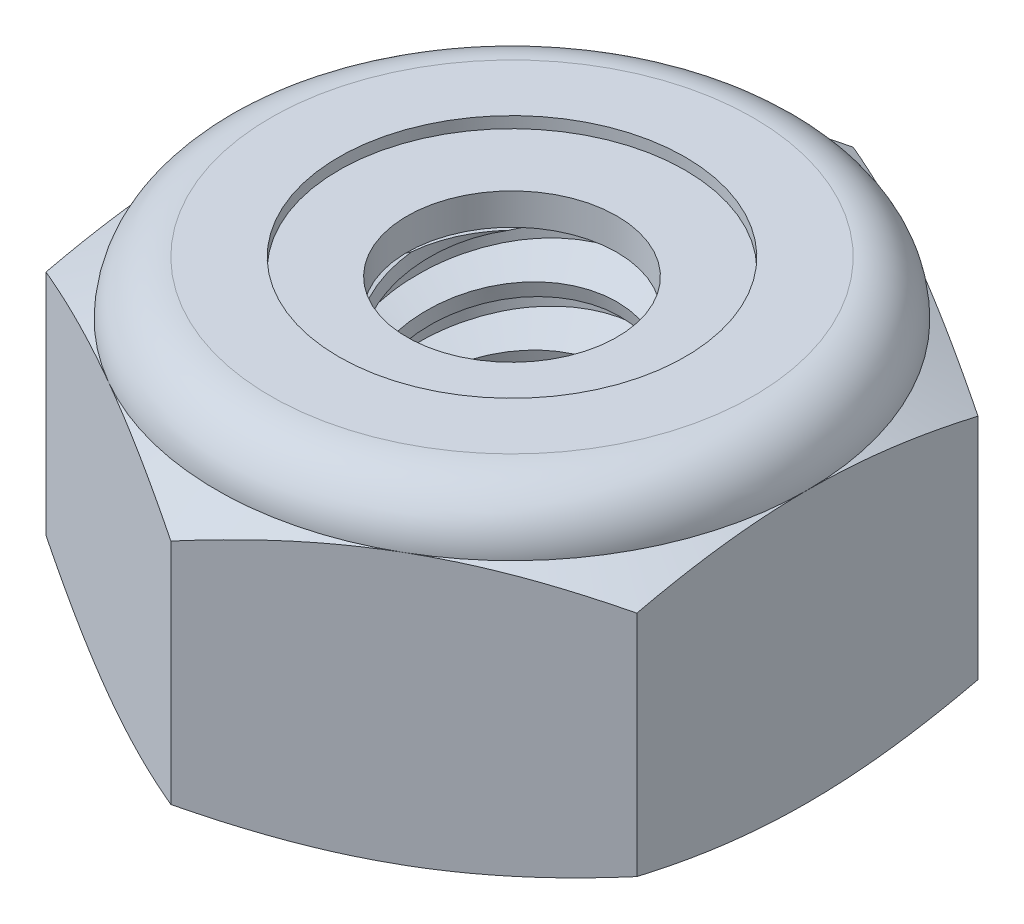
SolidWorks part; units mm, degrees
material "Alloy Steel"
ref_plane "Front" through (0, 0, 0) normal (0, 0, 1) x (1, 0, 0)
ref_plane "Top" through (0, 0, 0) normal (0, 1, 0) x (1, 0, 0)
ref_plane "Right" through (0, 0, 0) normal (1, 0, 0) x (0, 0, -1)
sketch "Sketch1" plane through (0, 0, 0) normal (0, 1, 0) x (1, 0, 0)
  line L1 (0, 4.5827) -> (-3.9688, 2.2914)
  line L2 (-3.9688, 2.2914) -> (-3.9688, -2.2914)
  line L3 (-3.9688, -2.2914) -> (0, -4.5827)
  line L4 (0, -4.5827) -> (3.9688, -2.2914)
  line L5 (3.9688, -2.2914) -> (3.9687, 2.2914)
  line L6 (3.9687, 2.2914) -> (0, 4.5827)
  circle A0 centre (0, 0) radius 3.9688 construction
  dimension "Hex Flats" = 7.9375
extrude "Extrude1" add sketch "Sketch1" along normal blind 4.3656
sketch "Sketch2" plane through (0, 0, 0) normal (1, 0, 0) x (0, 0, -1)
  line L0 (-1.7526, 0) -> (-1.7526, 4.3656) construction
  line L1 (0, 0) -> (1.7526, 0)
  line L2 (0, 0) -> (0, 4.3656)
  line L3 (0, 4.3656) -> (1.7526, 4.3656)
  line L4 (1.7526, 0) -> (1.7526, 4.3656)
  line L5 (-2.2914, 4.3656) -> (2.2914, 4.3656) construction
  line L7 (0, -1.7526) -> (0, 0) construction
  dimension "Thread Dia" = 3.5052
revolve "Revolve1" add sketch "Sketch2" angle 360 about L7
sketch "Sketch3" plane through (0, 0, 0) normal (1, 0, 0) x (0, 0, -1)
  line L0 (1.7526, 4.3656) -> (-1.7526, 4.3656) construction
  line L1 (-1.7526, 4.3656) -> (-1.7526, 3.5719) construction
  line L2 (-1.7526, 3.5719) -> (1.7526, 4.3656) construction
  line L3 (1.7526, 4.3656) -> (1.7745, 4.2689) construction
  line L4 (1.7745, 4.2689) -> (1.9279, 3.5915)
  line L5 (1.9279, 3.5915) -> (1.4541, 3.7385)
  line L6 (1.4541, 3.7385) -> (1.4103, 3.932)
  line L7 (1.4103, 3.932) -> (1.7745, 4.2689)
  line L8 (1.4322, 3.8353) -> (1.8512, 3.9302) construction
  line L9 (1.7526, 4.3656) -> (1.7526, 3.9078) construction
  line L10 (1.7526, 3.9078) -> (-1.7526, 3.1141) construction
  line L11 (-1.7526, 3.1141) -> (-1.7526, 3.5719) construction
  line L12 (-0.1935, 4.3656) -> (0.1935, 2.6563) construction
  line L13 (-1.7526, 0) -> (-1.7526, 4.3656) construction
  line L14 (0, 4.3656) -> (1.7526, 4.3656) construction
  line L15 (1.7526, 0) -> (1.7526, 4.3656) construction
  point P13 (0, 3.511)
  dimension "D1" = 0.0992
  dimension "D2" = 0.1984
  dimension "Thread Pitch" = 0.7937
  dimension "D4" = 60
  dimension "D5" = 0.7937
revolve "Cut-Revolve1" cut sketch "Sketch3" angle 360 about L12
pattern_linear "LPattern1" count 6 spacing 0.7937 along (0, -1, 0) count 2 spacing 0.7937 along (0, 1, 0) of "Cut-Revolve1"
sketch "Sketch4" plane through (0, 0, 0) normal (1, 0, 0) x (0, 0, -1)
  line L0 (0, 4.3656) -> (1.7526, 4.3656)
  line L1 (1.7526, 4.3656) -> (1.4103, 4.206)
  line L2 (1.4103, 4.206) -> (1.4103, 0.1596)
  line L3 (1.4103, 0.1596) -> (1.7526, 0)
  line L4 (1.7526, 0) -> (0, 0)
  line L5 (0, 0) -> (0, 4.3656)
  line L6 (1.7526, 0) -> (1.7526, 4.3656) construction
  line L7 (0, 4.3656) -> (1.7526, 4.3656) construction
  line L8 (0, 0) -> (1.7526, 0) construction
  line L9 (0, 0) -> (0, 4.3656) construction
  line L10 (0, 4.3656) -> (0, 4.7433) construction
  dimension "D1" = 25
revolve "Cut-Revolve2" cut sketch "Sketch4" angle 360 about L10
combine bodies "Combine1" operation type subtract main body 112 bodies to subtract 111
sketch "Sketch5" plane through (0, 0, 0) normal (1, 0, 0) x (0, 0, -1)
  line L0 (0, 0) -> (3.9688, 0)
  line L1 (3.9688, 0) -> (4.5827, 0.2863)
  line L2 (4.5827, 0.2863) -> (4.5827, 3.3517)
  line L3 (4.5827, 3.3517) -> (3.9687, 3.638)
  line L4 (3.2411, 4.3656) -> (3.2411, 5.6356)
  line L5 (3.2411, 5.6356) -> (5.8527, 5.6356)
  line L6 (5.8527, 5.6356) -> (5.8527, -1.27)
  line L7 (5.8527, -1.27) -> (0, -1.27)
  line L8 (0, -1.27) -> (0, 0)
  line L9 (3.9687, 3.638) -> (3.9688, 0) construction
  line L10 (0, 0) -> (1.7526, 0) construction
  line L13 (4.5827, 1.819) -> (5.8527, 1.819) construction
  line L14 (4.5827, 4.3656) -> (4.5827, 0) construction
  line L15 (0, 0) -> (0, 5.6356) construction
  line L20 (0, 5.6356) -> (3.2411, 5.6356) construction
  line L22 (0, 4.3656) -> (1.7526, 4.3656) construction
  arc A0 (3.9687, 3.638) -> (3.2411, 4.3656) centre (3.2411, 3.638) ccw
  dimension "D1" = 25
  dimension "D2" = 1.27
  dimension "D3" = 4.3656
  dimension "D4" = 0.7276
revolve "Cut-Revolve3" cut sketch "Sketch5" angle 360 about L15
sketch "Sketch6" plane through (0, 0, 0) normal (1, 0, 0) x (0, 0, -1)
  line L0 (0, 3.638) -> (3.8163, 3.638)
  line L1 (3.2411, 4.2132) -> (2.3257, 4.2132)
  line L2 (0, 5.6356) -> (0, 3.638)
  line L3 (2.3257, 5.6356) -> (0, 5.6356)
  line L4 (0, 5.6356) -> (3.2411, 5.6356) construction
  line L5 (0, 0) -> (0, 5.6356) construction
  line L6 (0, 5.6356) -> (0, 44.323) construction
  line L7 (2.3257, 4.2132) -> (2.3257, 5.6356)
  line L8 (3.2411, 4.3656) -> (3.2411, 4.2132) construction
  line L9 (2.3257, 4.2132) -> (1.4103, 4.2132) construction
  line L10 (1.4103, 4.2132) -> (1.4103, 4.206) construction
  arc A0 (3.8163, 3.638) -> (3.2411, 4.2132) centre (3.2411, 3.638) ccw
  arc A1 (3.9687, 3.638) -> (3.2411, 4.3656) centre (3.2411, 3.638) ccw construction
  dimension "D1" = 0.1524
revolve "Cut-Revolve4" cut sketch "Sketch6" angle 360 about L6
sketch "Sketch7" plane through (0, 0, 0) normal (1, 0, 0) x (0, 0, -1)
  line L0 (1.4103, 3.7142) -> (3.7343, 3.7142)
  line L1 (3.2411, 4.137) -> (1.4103, 4.137)
  line L2 (1.4103, 4.137) -> (1.4103, 3.7142)
  line L3 (1.4103, 3.7142) -> (0, 3.7142) construction
  line L4 (0, 3.7142) -> (0, 4.137) construction
  line L5 (0, 4.137) -> (1.4103, 4.137) construction
  line L6 (1.4103, 3.7142) -> (1.4103, 3.638) construction
  line L7 (0, 3.638) -> (3.8163, 3.638) construction
  line L8 (3.2411, 4.137) -> (3.2411, 4.2132) construction
  arc A0 (3.7343, 3.7142) -> (3.2411, 4.137) centre (3.2411, 3.638) ccw
  arc A2 (3.8163, 3.638) -> (3.2411, 4.2132) centre (3.2411, 3.638) ccw construction
  dimension "D1" = 0.0762
revolve "Revolve2" add sketch "Sketch7" angle 360 about L4
equation "\"D1@Sketch3\"=\"Thread Pitch@Sketch3\"/8"
equation "\"D2@Sketch3\"=\"Thread Pitch@Sketch3\"/4"
equation "\"D5@Sketch3\"=\"Thread Pitch@Sketch3\""
equation "\"D4@LPattern1\"=\"Thread Pitch@Sketch3\""
equation "\"D3@LPattern1\"=\"Thread Pitch@Sketch3\""
equation "\"D1@LPattern1\"=\"Height@Extrude1\"/\"Thread Pitch@Sketch3\""
equation "\"D4@Sketch5\"=\"Height@Extrude1\"/6"
